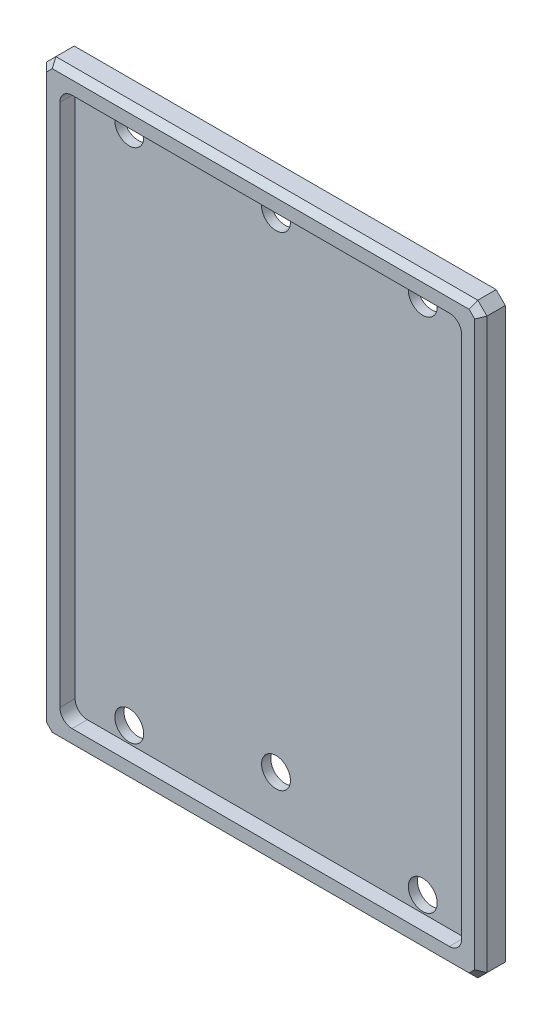
SolidWorks part; units mm, degrees
material "AISI 304"
ref_plane "Front Plane" through (0, 0, 0) normal (0, 0, 1) x (1, 0, 0)
ref_plane "Top Plane" through (0, 0, 0) normal (0, 1, 0) x (1, 0, 0)
ref_plane "Right Plane" through (0, 0, 0) normal (1, 0, 0) x (0, 0, -1)
sketch "Sketch1" plane through (0, 0, 0) normal (0, 0, 1) x (1, 0, 0)
  line L1 (114.3, -152.4) -> (-114.3, -152.4)
  line L2 (114.3, -152.4) -> (114.3, 152.4)
  line L3 (114.3, 152.4) -> (-114.3, 152.4)
  line L4 (-114.3, -152.4) -> (-114.3, 152.4)
  line L5 (114.3, -152.4) -> (-114.3, 152.4) construction
  line L6 (114.3, 152.4) -> (-114.3, -152.4) construction
  point P0 (0, 0)
  dimension "D1" = 228.6
  dimension "D2" = 304.8
extrude "Boss-Extrude1" add sketch "Sketch1" along normal blind 12.7
sketch "Sketch2" plane through (0, 0, 12.7) normal (0, 0, 1) x (1, 0, 0)
  line L0 (-114.3, 152.4) -> (-114.3, -152.4) construction
  line L1 (97.95, -142.4) -> (-97.95, -142.4)
  line L2 (104.3, -136.05) -> (104.3, 136.05)
  line L3 (97.95, 142.4) -> (-97.95, 142.4)
  line L4 (-104.3, -136.05) -> (-104.3, 136.05)
  line L5 (104.3, -142.4) -> (-104.3, 142.4) construction
  line L6 (104.3, 142.4) -> (-104.3, -142.4) construction
  line L7 (114.3, 152.4) -> (-114.3, 152.4) construction
  arc A0 (-97.95, -142.4) -> (-104.3, -136.05) centre (-97.95, -136.05) cw
  arc A1 (97.95, -142.4) -> (104.3, -136.05) centre (97.95, -136.05) ccw
  arc A2 (104.3, 136.05) -> (97.95, 142.4) centre (97.95, 136.05) ccw
  arc A3 (-97.95, 142.4) -> (-104.3, 136.05) centre (-97.95, 136.05) ccw
  point P0 (0, 0)
  dimension "D3" = 6.35
  dimension "D1" = 10
  dimension "D2" = 10
extrude "Cut-Extrude1" cut sketch "Sketch2" against normal blind 7.9375
sketch "Sketch4" plane through (0, 0, 4.7625) normal (0, 0, 1) x (1, 0, 0)
  line L0 (-97.95, -142.4) -> (97.95, -142.4) construction
  line L1 (97.95, 142.4) -> (-97.95, 142.4) construction
  line L4 (-114.3, 152.4) -> (-114.3, -152.4) construction
  line L5 (114.3, -152.4) -> (114.3, 152.4) construction
  line L8 (-97.95, -142.4) -> (97.95, -142.4) construction
  circle A0 centre (-76.2, 134.05) radius 7.5
  circle A1 centre (76.2, 134.05) radius 7.5
  circle A2 centre (-76.2, -134.05) radius 7.5
  circle A3 centre (76.2, -134.05) radius 7.5
  circle A4 centre (0, 134.05) radius 7.5
  circle A5 centre (0, -117) radius 7.5
  point P15 (0, 0)
  dimension "D1" = 15
  dimension "D2" = 15
  dimension "D3" = 15
  dimension "D4" = 15
  dimension "D13" = 15
  dimension "D14" = 15
  dimension "D15" = 8.35
  dimension "D5" = 0
  dimension "D6" = 38.1
  dimension "D7" = 38.1
  dimension "D8" = 0
  dimension "D9" = 8.35
  dimension "D10" = 38.1
  dimension "D11" = 38.1
  dimension "D16" = 25.4
extrude "Cut-Extrude2" cut sketch "Sketch4" against normal through all
hole_wizard "M4x0.7 Tapped Hole1" positions "Sketch8" profile "Sketch9" tap size "M4x0.7" standard "ANSI Metric"
sketch "Sketch8" plane through (0, 0, 0) normal (0, 0, -1) x (-1, 0, 0)
  line L0 (114.3, -152.4) -> (-114.3, -152.4) construction
  line L1 (-114.3, -152.4) -> (-114.3, 152.4) construction
  point P0 (-111.125, -102.4)
  point P2 (-111.125, 0)
  point P4 (-111.125, 113.6)
  point P14 (-114.3, 0)
  dimension "D1" = 266
  dimension "D2" = 3.175
  dimension "D3" = 50
sketch "Sketch9" plane through (111.125, -102.4, 0) normal (1, 0, 0) x (0, 1, 0)
  line L0 (0, 0) -> (0, 6.3914)
  line L1 (0, 6.3914) -> (1.65, 5.4)
  line L2 (1.65, 5.4) -> (1.65, 0)
  line L5 (1.65, 0) -> (0, 0)
  line L10 (0, 6.3914) -> (-1.65, 5.4) construction
  line L11 (0, -6.35) -> (0, 107.95) construction
  dimension "Tap Drill Dia." = 3.3
  dimension "Tap Drill Depth" = 5.4
  dimension "Drill Angle" = 118
cosmetic thread "Hole Thread1" parameters "D1"=3, "D2"=4.3
cosmetic thread "Hole Thread2" parameters "D1"=3, "D2"=4.3
cosmetic thread "Hole Thread3" parameters "D1"=3, "D2"=4.3
chamfer "Chamfer1" distance 4.7625 angle 45 4 edges at (-114.3, -152.4, 6.35) (114.3, -152.4, 6.35) (-114.3, 152.4, 6.35) (114.3, 152.4, 6.35)
chamfer "Chamfer2" distance 3.175 angle 45 8 edges at (-111.9188, 150.0187, 12.7) (0, 152.4, 12.7) (111.9187, 150.0187, 12.7) (114.3, 0, 12.7) (111.9187, -150.0188, 12.7) (0, -152.4, 12.7) (-111.9188, -150.0188, 12.7) (-114.3, 0, 12.7)
